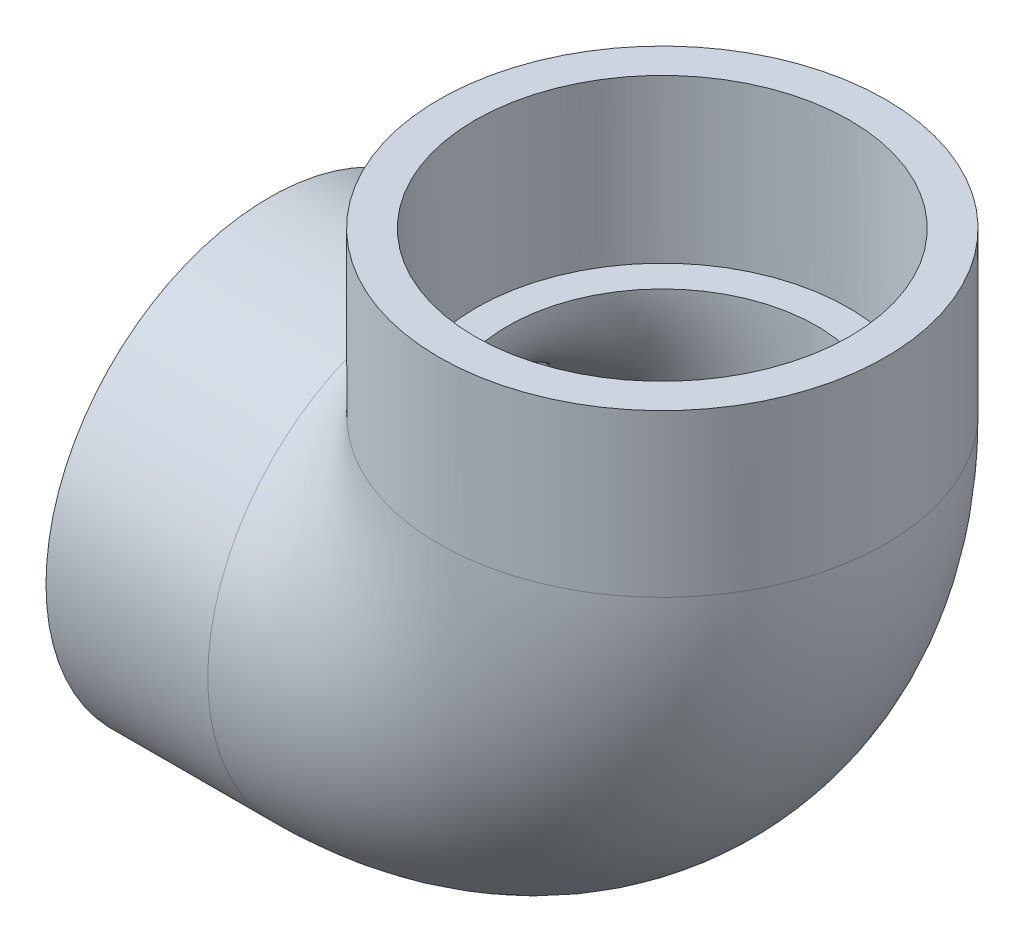
SolidWorks part; units mm, degrees
ref_plane "Front Plane" through (0, 0, 0) normal (0, 0, 1) x (1, 0, 0)
ref_plane "Top Plane" through (0, 0, 0) normal (0, 1, 0) x (1, 0, 0)
ref_plane "Right Plane" through (0, 0, 0) normal (1, 0, 0) x (0, 0, -1)
sketch "Sketch0" plane through (0, 0, 0) normal (0, 0, 1) x (1, 0, 0)
  line L0 (-93.6625, 0) -> (0, 0) construction
  line L1 (0, 0) -> (0, 93.6625) construction
  line L2 (-55.118, 0) -> (0, 0) construction
  line L3 (0, 0) -> (0, 55.118) construction
  line L4 (-93.6625, 53.213) -> (-93.6625, -53.213) construction
  line L5 (-55.118, 44.3484) -> (-93.6625, 44.6532) construction
  line L6 (-55.118, 44.3484) -> (-55.118, -44.3484) construction
  line L7 (-55.118, -44.3484) -> (-93.6625, -44.6532) construction
  line L8 (-93.6625, 44.6532) -> (-93.6625, -44.6532) construction
  line L9 (-53.213, 93.6625) -> (53.213, 93.6625) construction
  line L10 (-44.6532, 93.6625) -> (44.6532, 93.6625) construction
  line L11 (44.6532, 93.6625) -> (44.3484, 55.118) construction
  line L12 (44.3484, 55.118) -> (-44.3484, 55.118) construction
  line L13 (-44.3484, 55.118) -> (-44.6532, 93.6625) construction
  line L14 (-55.118, 36.83) -> (-55.118, -36.83) construction
  line L18 (-36.83, 55.118) -> (36.83, 55.118) construction
  dimension "H" = 93.6625
  dimension "G" = 55.118
  dimension "M" = 106.426
  dimension "OD A" = 89.3064
  dimension "OD B" = 88.6968
  dimension "ID" = 73.66
sketch "Sketch1" plane through (0, 0, 0) normal (0, 0, 1) x (1, 0, 0)
  line L0 (-93.6625, 0) -> (0, 0) construction
  line L1 (-93.6625, 0) -> (0, 0) construction
  line L3 (-93.6625, -53.213) -> (-55.118, -53.213)
  line L4 (-93.6625, -53.213) -> (-93.6625, -44.6532)
  line L5 (-93.6625, -44.6532) -> (-55.118, -44.3484)
  line L6 (-55.118, -53.213) -> (-55.118, -44.3484)
revolve "Revolve1" add sketch "Sketch1" angle 360 about L1
sketch "Sketch2" plane through (0, 0, 0) normal (0, 0, 1) x (1, 0, 0)
  line L0 (44.6532, 93.6625) -> (44.3484, 55.118)
  line L1 (44.3484, 55.118) -> (53.213, 55.118)
  line L2 (53.213, 55.118) -> (53.213, 93.6625)
  line L3 (53.213, 93.6625) -> (44.6532, 93.6625)
  line L4 (0, 0) -> (0, 93.6625) construction
  line L5 (0, 0) -> (0, 93.6625) construction
revolve "Revolve2" add sketch "Sketch2" angle 360 about L5
sketch "Sketch3" plane through (-55.118, 0, 0) normal (1, 0, 0) x (0, 0, -1)
  circle A0 centre (0, 0) radius 36.83
  circle A1 centre (0, 0) radius 53.213
sketch "Sketch4" plane through (0, 0, 0) normal (0, 0, 1) x (1, 0, 0)
  line L0 (-93.6625, 0) -> (0, 0) construction
  line L1 (0, 0) -> (0, 93.6625) construction
  line L2 (-93.6625, 0) -> (-55.118, 0) construction
  line L3 (0, 55.118) -> (0, 93.6625) construction
  arc A0 (-55.118, 0) -> (0, 55.118) centre (-55.118, 55.118) ccw
sweep "Sweep1" add profiles "Sketch3" path "Sketch4"
other "CPoint1" parameters "Diameter"=76.2, "StubLength"=76.2
ref_axis "Axis1" through (-65.118, 0, 0) along (1, 0, 0)
other "CPoint2" parameters "Diameter"=76.2, "StubLength"=76.2
ref_axis "Axis2" through (0, 65.118, 0) along (0, -1, 0)
other "RPoint1"
